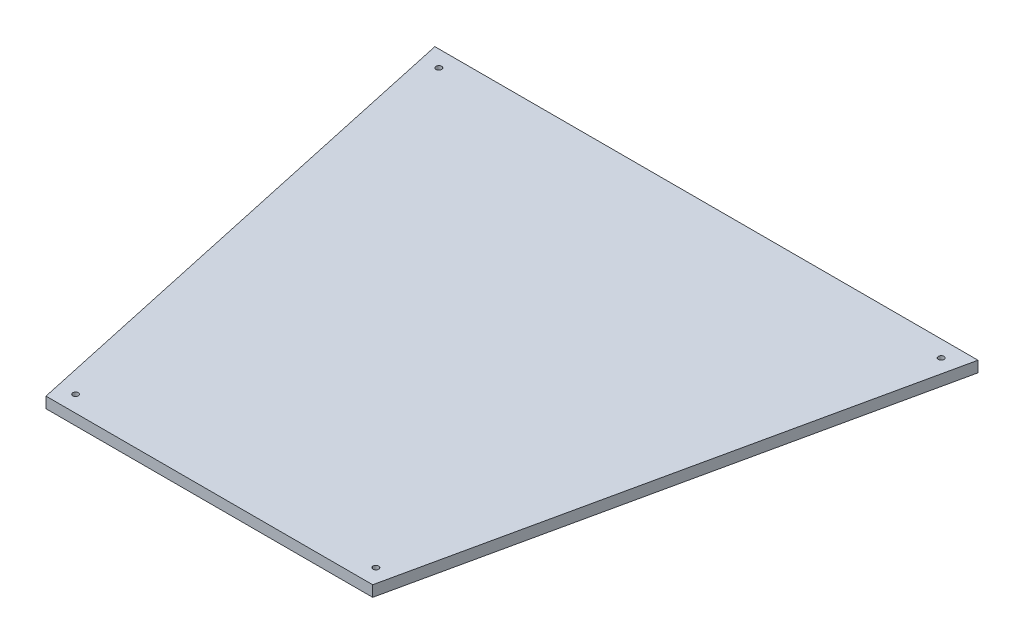
SolidWorks part; units mm, degrees
ref_plane "Front Plane" through (0, 0, 0) normal (0, 0, 1) x (1, 0, 0)
ref_plane "Top Plane" through (0, 0, 0) normal (0, 1, 0) x (1, 0, 0)
ref_plane "Right Plane" through (0, 0, 0) normal (1, 0, 0) x (0, 0, -1)
ref_plane "Plane1" through (0, -28.575, 0) normal (0, -1, 0) x (-1, 0, 0)
sketch "Sketch1" plane through (4.556, 0, 422.8773) normal (0, -1, 0) x (-1, 0, 0)
  line L0 (-184.8912, -195.6635) -> (194.0158, -195.6512)
  line L1 (194.0158, -195.6512) -> (319.5099, 380.9014)
  line L2 (319.5099, 380.9014) -> (-310.4226, 380.881)
  line L3 (-310.4226, 380.881) -> (-184.8912, -195.6635)
  line L4 (-310.4239, 380.881) -> (319.5112, 380.9014) construction
  line L5 (-184.7475, -196.3231) -> (-311.7795, 387.1133) construction
  line L6 (320.8664, 387.1338) -> (193.8722, -196.3108) construction
  line L7 (194.0184, -195.6512) -> (-184.8937, -195.6635) construction
extrude "Boss-Extrude1" add sketch "Sketch1" along normal blind 12.7
sketch "Sketch2" plane through (0, 0, 0) normal (0, 1, 0) x (1, 0, 0)
  circle A28 centre (-174.1239, -599.4885) radius 3.2639
  circle A30 centre (-174.1239, -599.4885) radius 3.2639
  circle A32 centre (174.085, -599.501) radius 3.2639
  circle A33 centre (174.085, -599.501) radius 3.2639
  circle A34 centre (291.3209, -61.0565) radius 3.2639
  circle A35 centre (291.3209, -61.0565) radius 3.2639
  circle A36 centre (-291.3249, -61.0376) radius 3.2639
  circle A37 centre (-291.3249, -61.0376) radius 3.2639
  dimension "D7" = 0
  dimension "D8" = 0
  dimension "D9" = 0
  dimension "D13" = 0
extrude "Cut-Extrude1" cut sketch "Sketch2" against normal through all
